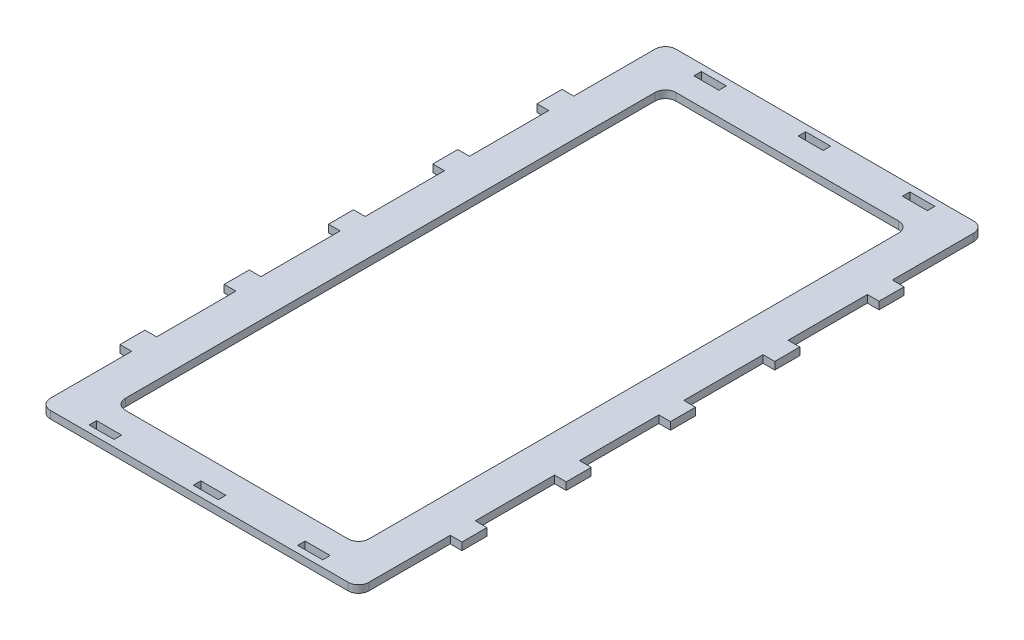
SolidWorks part; units mm, degrees
ref_plane "前视基准面" through (0, 0, 0) normal (0, 0, 1) x (1, 0, 0)
ref_plane "上视基准面" through (0, 0, 0) normal (0, 1, 0) x (1, 0, 0)
ref_plane "右视基准面" through (0, 0, 0) normal (1, 0, 0) x (0, 0, -1)
other "Configuration Table"
sketch "草图1" plane through (0, 0, 0) normal (0, 1, 0) x (1, 0, 0)
  line L1 (-382, 750) -> (382, 750)
  line L2 (-382, 750) -> (-382, -750)
  line L3 (-382, -750) -> (382, -750)
  line L4 (382, 750) -> (382, -750)
  line L5 (-410, -470) -> (-382, -470)
  line L6 (-410, -470) -> (-410, -530)
  line L7 (-410, -530) -> (-382, -530)
  line L8 (-382, -470) -> (-382, -530)
  line L9 (-280, -734) -> (-220, -734)
  line L10 (-280, -734) -> (-280, -716)
  line L11 (-280, -716) -> (-220, -716)
  line L12 (-220, -734) -> (-220, -716)
  line L13 (-292, 660) -> (292, 660)
  line L14 (-292, 660) -> (-292, -660)
  line L15 (-292, -660) -> (292, -660)
  line L16 (292, 660) -> (292, -660)
  point P4 (-382, 0)
  point P6 (0, -750)
  point P11 (-410, -500)
  point P20 (0, -660)
  point P21 (-292, 0)
  point P22 (-250, -734)
  point P23 (-220, -725)
  dimension "D1" = 764
  dimension "D2" = 1500
  dimension "D3" = 250
  dimension "D4" = 28
  dimension "D5" = 60
  dimension "D6" = 90
  dimension "D7" = 90
  dimension "D8" = 60
  dimension "D9" = 18
  dimension "D10" = 132
  dimension "D11" = 25
extrude "凸台-拉伸1" add sketch "草图1" along normal blind 18 contours L2 L3 L4 L1 | L14 L15 L16 L13
extrude "凸台-拉伸2" add sketch "草图1<3>" along normal up to surface (18 mm away) contours L6 L7 L8 L5 up to face at (0, 18, 0)
sketch "草图1<3>" plane through (0, 0, 0) normal (0, 1, 0) x (1, 0, 0) same geometry as "草图1"
pattern_linear "阵列(线性)1" count 5 spacing 250 along (0, 0, -1) of "凸台-拉伸2"
mirror "镜向1" about plane through (0, 0, 0) normal (1, 0, 0) of "阵列(线性)1", "凸台-拉伸2"
extrude "切除-拉伸1" cut sketch "草图1<4>" along normal through all contours L12 L11 L10 L9
sketch "草图1<4>" plane through (0, 0, 0) normal (0, 1, 0) x (1, 0, 0) same geometry as "草图1"
pattern_linear "阵列(线性)2" count 3 spacing 250 along (1, 0, 0) of "切除-拉伸1"
mirror "镜向2" about plane through (0, 0, 0) normal (0, 0, 1) of "阵列(线性)2", "切除-拉伸1"
fillet "圆角1" radius 25 4 edges at (-382, 9, -750) (382, 9, -750) (382, 9, 750) (-382, 9, 750)
fillet "圆角2" radius 25 4 edges at (-292, 9, -660) (292, 9, -660) (292, 9, 660) (-292, 9, 660)
